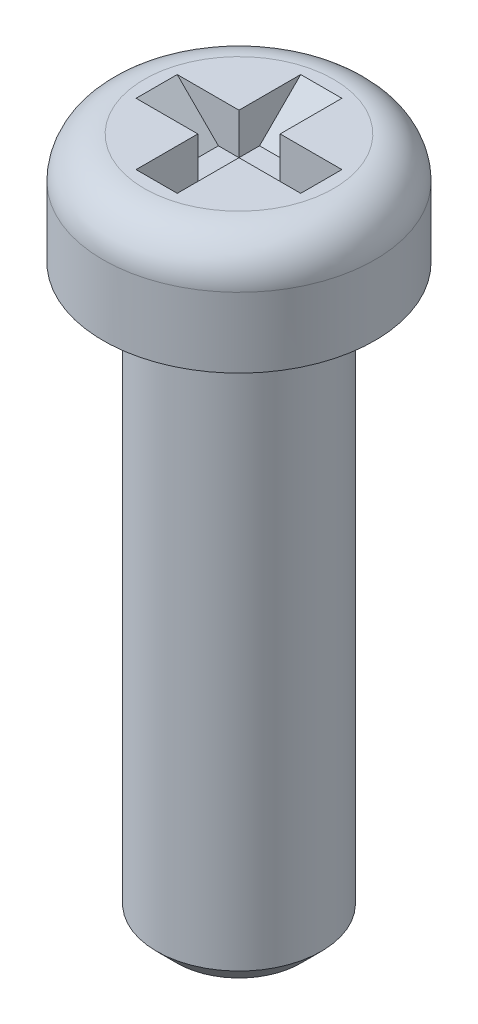
SolidWorks part; units mm, degrees
ref_plane "前视基准面" through (0, 0, 0) normal (0, 0, 1) x (1, 0, 0)
ref_plane "上视基准面" through (0, 0, 0) normal (0, 1, 0) x (1, 0, 0)
ref_plane "右视基准面" through (0, 0, 0) normal (1, 0, 0) x (0, 0, -1)
other "Configuration Table"
sketch "草图1" plane through (0, 0, 0) normal (0, 1, 0) x (1, 0, 0)
  circle A0 centre (0, 0) radius 2
  dimension "D1" = 4
extrude "凸台-拉伸1" add sketch "草图1" along normal blind 14
cosmetic thread "装饰螺纹线1" parameters "D2"=3
sketch "草图2" plane through (0, 14, 0) normal (0, 1, 0) x (1, 0, 0)
  circle A0 centre (0, 0) radius 3.3
  dimension "D1" = 6.6
extrude "凸台-拉伸2" add sketch "草图2" along normal blind 2.7
fillet "圆角1" radius 1 1 edges at (0, 16.7, 3.3)
chamfer "倒角1" distance 0.5 angle 45 1 edges at (0, 0, 2)
sketch "草图3" plane through (0, 16.7, 0) normal (0, 1, 0) x (1, 0, 0)
  line L0 (-2, 0) -> (2, 0)
  line L1 (0, 2) -> (0, -2)
  point P5 (0, 0)
  point P9 (0, 0)
  dimension "D1" = 4
  dimension "D2" = 4
extrude "切除-拉伸-薄壁1" cut sketch "草图3" against normal blind 1 thin thin type mid plane wall 1
chamfer "倒角2" distance 1 angle 45 4 edges at (0, 15.7, 2) (2, 15.7, 0) (0, 15.7, -2) (-2, 15.7, 0)
